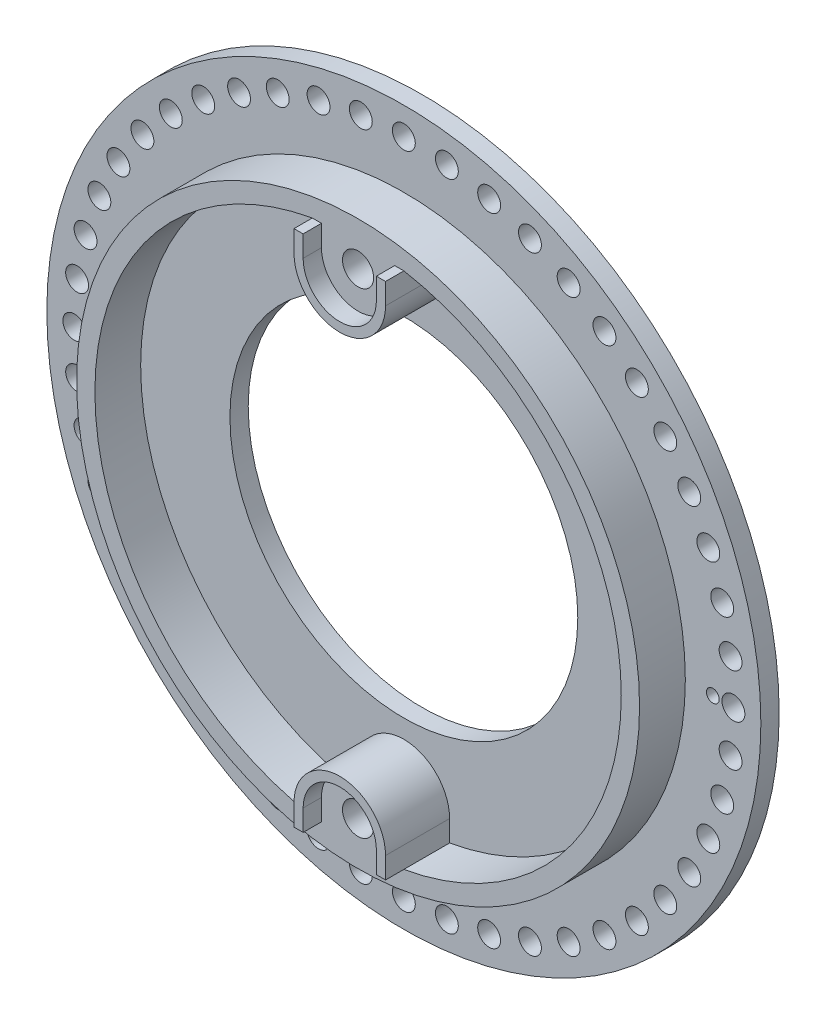
SolidWorks part; units mm, degrees
ref_plane "Front Plane" through (0, 0, 0) normal (0, 0, 1) x (1, 0, 0)
ref_plane "Top Plane" through (0, 0, 0) normal (0, 1, 0) x (1, 0, 0)
ref_plane "Right Plane" through (0, 0, 0) normal (1, 0, 0) x (0, 0, -1)
sketch "Sketch1" plane through (0, 0, 0) normal (0, 0, 1) x (1, 0, 0)
  circle A0 centre (0, 0) radius 39
  dimension "D1" = 78
extrude "Boss-Extrude1" add sketch "Sketch1" along normal blind 2
sketch "Sketch3" plane through (0, 0, 2) normal (0, 0, 1) x (1, 0, 0)
  line L0 (-5, 26) -> (-5, 28.3119)
  line L1 (5, 26) -> (5, 28.3119)
  line L2 (5, -26) -> (5, -28.3119)
  line L3 (-5, -26) -> (-5, -28.3119)
  circle A0 centre (0, 0) radius 30.75
  arc A1 (-5, 28.3119) -> (-5, -28.3119) centre (0, 0) ccw
  arc A2 (-5, 26) -> (5, 26) centre (0, 26) ccw
  circle A3 centre (0, 0) radius 28.75 construction
  arc A4 (5, -26) -> (-5, -26) centre (0, -26) ccw
  arc A5 (5, -28.3119) -> (5, 28.3119) centre (0, 0) ccw
  point P18 (0, 0)
  point P22 (-0.2453, 0)
  dimension "D1" = 61.5
  dimension "D3" = 10
  dimension "D5" = 2
  dimension "D4" = 26
  dimension "D2" = 2
extrude "Boss-Extrude2" add sketch "Sketch3" along normal blind 5 contours A1 L3 A4 L2 A5 L1 A2 L0 | A0
sketch "Sketch5" plane through (0, 0, 7) normal (0, 0, 1) x (1, 0, 0)
  circle A0 centre (0, -26) radius 1.7
  circle A1 centre (0, 26) radius 1.7
  point P7 (0, 0)
  dimension "D1" = 26
  dimension "D2" = 3.4
  dimension "D3" = 2
  dimension "D4" = 52
extrude "Cut-Extrude2" cut sketch "Sketch5" against normal up to surface (7 mm away) up to face at (39, 0, 0)
sketch "Sketch6" plane through (0, 0, 0) normal (0, 0, -1) x (-1, 0, 0)
  circle A0 centre (0, 26) radius 3
  circle A1 centre (0, -26) radius 3
  dimension "D1" = 6
  dimension "D2" = 6
  dimension "D3" = 26
  dimension "D4" = 26
extrude "Cut-Extrude3" cut sketch "Sketch6" against normal blind 4.5
sketch "Sketch7" plane through (0, 0, 0) normal (0, 0, -1) x (-1, 0, 0)
  circle A0 centre (0, 0) radius 19
  dimension "D1" = 38
extrude "Cut-Extrude4" cut sketch "Sketch7" against normal up to surface (2 mm away) up to face at (0, 0, 2)
sketch "Sketch8" plane through (0, 0, 2) normal (0, 0, 1) x (1, 0, 0)
  circle A0 centre (36, 0) radius 1.25
  circle A1 centre (35.692, -4.6989) radius 1.25
  circle A2 centre (34.7733, -9.3175) radius 1.25
  circle A3 centre (33.2597, -13.7766) radius 1.25
  circle A4 centre (31.1769, -18) radius 1.25
  circle A5 centre (28.5607, -21.9154) radius 1.25
  circle A6 centre (25.4558, -25.4558) radius 1.25
  circle A7 centre (21.9154, -28.5607) radius 1.25
  circle A8 centre (18, -31.1769) radius 1.25
  circle A9 centre (13.7766, -33.2597) radius 1.25
  circle A10 centre (9.3175, -34.7733) radius 1.25
  circle A11 centre (4.6989, -35.692) radius 1.25
  circle A12 centre (0, -36) radius 1.25
  circle A13 centre (-4.6989, -35.692) radius 1.25
  circle A14 centre (-9.3175, -34.7733) radius 1.25
  circle A15 centre (-13.7766, -33.2597) radius 1.25
  circle A16 centre (-18, -31.1769) radius 1.25
  circle A17 centre (-21.9154, -28.5607) radius 1.25
  circle A18 centre (-25.4558, -25.4558) radius 1.25
  circle A19 centre (-28.5607, -21.9154) radius 1.25
  circle A20 centre (-31.1769, -18) radius 1.25
  circle A21 centre (-33.2597, -13.7766) radius 1.25
  circle A22 centre (-34.7733, -9.3175) radius 1.25
  circle A23 centre (-35.692, -4.6989) radius 1.25
  circle A24 centre (-36, 0) radius 1.25
  circle A25 centre (-35.692, 4.6989) radius 1.25
  circle A26 centre (-34.7733, 9.3175) radius 1.25
  circle A27 centre (-33.2597, 13.7766) radius 1.25
  circle A28 centre (-31.1769, 18) radius 1.25
  circle A29 centre (-28.5607, 21.9154) radius 1.25
  circle A30 centre (-25.4558, 25.4558) radius 1.25
  circle A31 centre (-21.9154, 28.5607) radius 1.25
  circle A32 centre (-18, 31.1769) radius 1.25
  circle A33 centre (-13.7766, 33.2597) radius 1.25
  circle A34 centre (-9.3175, 34.7733) radius 1.25
  circle A35 centre (-4.6989, 35.692) radius 1.25
  circle A36 centre (0, 36) radius 1.25
  circle A37 centre (4.6989, 35.692) radius 1.25
  circle A38 centre (9.3175, 34.7733) radius 1.25
  circle A39 centre (13.7766, 33.2597) radius 1.25
  circle A40 centre (18, 31.1769) radius 1.25
  circle A41 centre (21.9154, 28.5607) radius 1.25
  circle A42 centre (25.4558, 25.4558) radius 1.25
  circle A43 centre (28.5607, 21.9154) radius 1.25
  circle A44 centre (31.1769, 18) radius 1.25
  circle A45 centre (33.2597, 13.7766) radius 1.25
  circle A46 centre (34.7733, 9.3175) radius 1.25
  circle A47 centre (35.692, 4.6989) radius 1.25
  point P104 (0, 0)
  dimension "D1" = 36
  dimension "D2" = 2.5
  dimension "D3" = 48
extrude "Cut-Extrude5" cut sketch "Sketch8" against normal up to surface (2 mm away) up to face at (-19, 0, 0)
fillet "Fillet1" radius 1.5 2 edges at (-3, -26, 4.5) (-3, 26, 4.5)
sketch "Sketch9" plane through (0, 0, 7) normal (0, 0, 1) x (1, 0, 0)
  line L2 (-4, 28.3119) -> (-5, 28.3119)
  line L3 (4, 28.3119) -> (5, 28.3119)
  line L4 (4, 28.3119) -> (4, 26)
  line L5 (-4, 26) -> (-4, 28.3119)
  line L6 (4, 28.3119) -> (4, 26)
  line L7 (-4, 26) -> (-4, 28.3119)
  line L8 (-5, 28.3119) -> (-5, 26)
  line L9 (5, 26) -> (5, 28.3119)
  line L10 (-5, -26) -> (-5, -28.3119)
  line L11 (-4, -28.3119) -> (-5, -28.3119)
  line L12 (-4, -28.3119) -> (-4, -26)
  line L13 (4, -26) -> (4, -28.3119)
  line L14 (4, -28.3119) -> (5, -28.3119)
  line L15 (5, -28.3119) -> (5, -26)
  arc A2 (4, -26) -> (-4, -26) centre (0, -26) ccw
  arc A4 (-5, 26) -> (5, 26) centre (0, 26) ccw
  arc A5 (-4, 26) -> (4, 26) centre (0, 26) ccw
  arc A6 (-4, 26) -> (4, 26) centre (0, 26) ccw
  arc A8 (5, -26) -> (-5, -26) centre (0, -26) ccw
  point P26 (0, 0)
  dimension "D1" = 2
  dimension "D2" = 1
extrude "Boss-Extrude3" add sketch "Sketch9" along normal blind 2
sketch "Alignment_Hole" plane through (0, 0, 0) normal (0, 0, -1) x (-1, 0, 0)
  circle A0 centre (-33.75, 0) radius 0.7
  circle A2 centre (-36, 0) radius 1.25 construction
  dimension "D1" = 1.4
  dimension "D2" = 2.25
extrude "Alignment_Hole - Cut" cut sketch "Alignment_Hole" against normal through all both and the other way through all
equation "\"D2@Sketch6\"=\"D1@Sketch6\""
